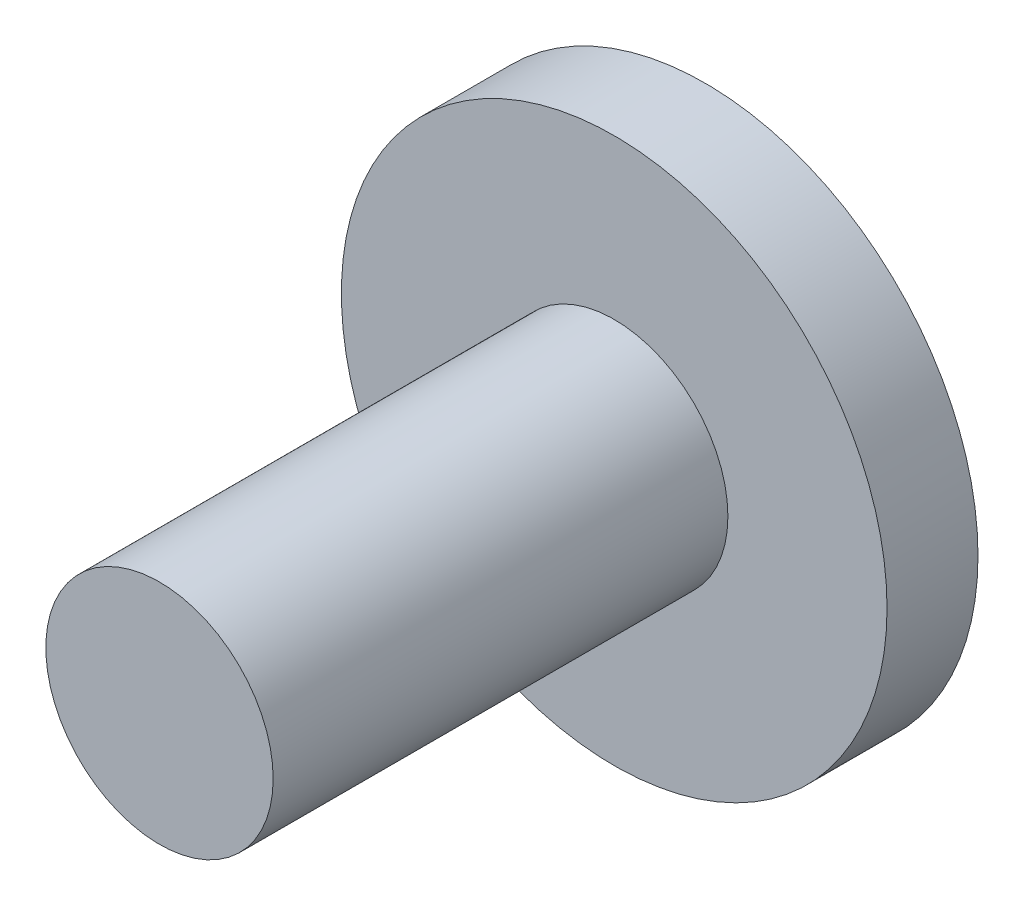
SolidWorks part; units mm, degrees
ref_plane "Front Plane" through (0, 0, 0) normal (0, 0, 1) x (1, 0, 0)
ref_plane "Top Plane" through (0, 0, 0) normal (0, 1, 0) x (1, 0, 0)
ref_plane "Right Plane" through (0, 0, 0) normal (1, 0, 0) x (0, 0, -1)
sketch "Sketch1" plane through (0, 0, 0) normal (0, 0, 1) x (1, 0, 0)
  circle A0 centre (0, 0) radius 6
  circle A1 centre (0, 0) radius 2.5
  circle A2 centre (0, 0) radius 4
  dimension "D1" = 5
  dimension "D2" = 12
  dimension "D3" = 8
extrude "Boss-Extrude1" add sketch "Sketch1" along normal blind 10 contours A1
extrude "Boss-Extrude2" add sketch "Sketch1<4>" against normal blind 2 separate body contours A0 A2 | A2 A1 | A1 region at (-5.8303, 0, 0) region at (0, 0, 0) region at (-3.8869, 0, 0)
sketch "Sketch1<4>" plane through (0, 0, 0) normal (0, 0, 1) x (1, 0, 0) same geometry as "Sketch1"
